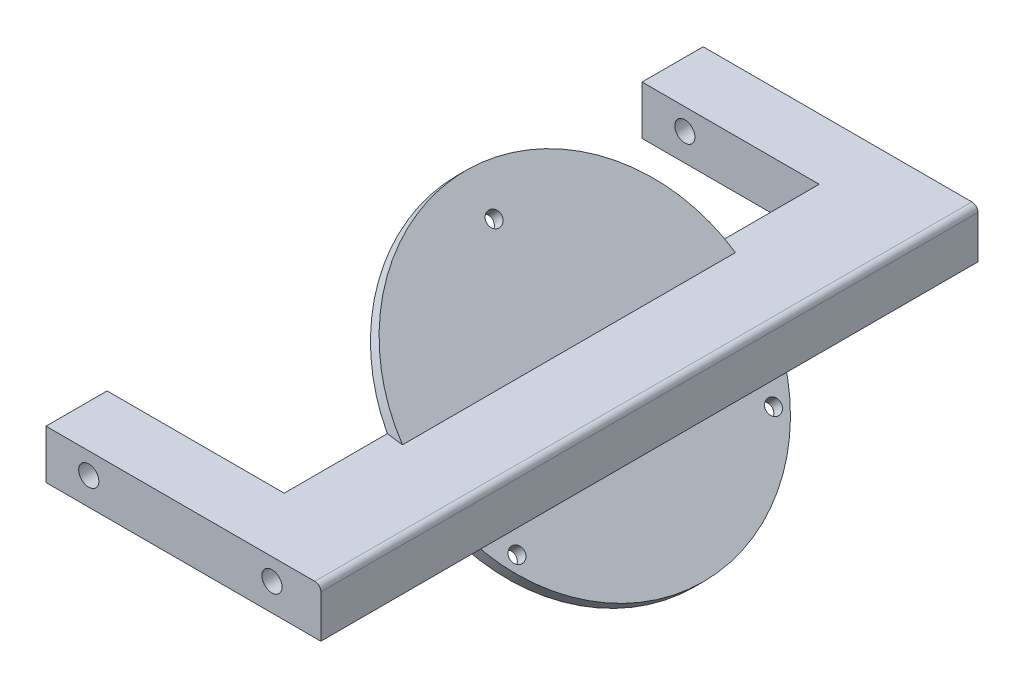
SolidWorks part; units mm, degrees
material "Nylon 101"
ref_plane "Front Plane" through (0, 0, 0) normal (0, 0, 1) x (1, 0, 0)
ref_plane "Top Plane" through (0, 0, 0) normal (0, 1, 0) x (1, 0, 0)
ref_plane "Right Plane" through (0, 0, 0) normal (1, 0, 0) x (0, 0, -1)
sketch "Sketch1" plane through (0, 0, 0) normal (0, 0, 1) x (1, 0, 0)
  line L4 (8, 4) -> (-8, 4)
  line L6 (0, -4) -> (-8, 4)
  line L7 (0, 4) -> (0, -4) construction
  line L8 (8, 4) -> (8, -4)
  line L9 (8, -4) -> (0, -4)
  dimension "D1" = 8
  dimension "D2" = 45
extrude "Base" add sketch "Sketch1" along normal mid plane 107.6
sketch "Sketch4" plane through (-2, -2, 0) normal (-0.7071, -0.7071, 0) x (0, 0, 1)
  line L0 (-53.8, 2.8284) -> (53.8, 2.8284) construction
  line L1 (-53.8, 8.4853) -> (-53.8, -2.8284) construction
  line L2 (53.8, 8.4853) -> (53.8, -2.8284) construction
  line L3 (0, 8.4853) -> (0, -2.8284) construction
  line L4 (53.8, 8.4853) -> (-53.8, 8.4853) construction
  line L6 (53.8, -2.8284) -> (-53.8, -2.8284) construction
  line L7 (-17.5, 20.3284) -> (17.5, 20.3284)
  line L8 (-17.5, 20.3284) -> (-17.5, -14.6716)
  line L9 (-17.5, -14.6716) -> (17.5, -14.6716)
  line L10 (17.5, 20.3284) -> (17.5, -14.6716)
  line L11 (-17.5, 20.3284) -> (17.5, -14.6716) construction
  line L12 (-17.5, -14.6716) -> (17.5, 20.3284) construction
  circle A0 centre (0, 2.8284) radius 27.5
  point P16 (0, 2.8284)
  point P17 (0, 2.8284)
  line M5 (53.8, 8.4853) -> (-53.8, 8.4853)
  dimension "D1" = 55
  dimension "D2" = 35
extrude "Boss-Extrude2" add sketch "Sketch4" against normal blind 2 contours A0 L8 L7 L10 M5 | L10 L7 L8 M5 | A0 L10 L9 L8 | A0 L8 M5 | L10 L8 L9 | L10 L8 M5 | A0 L10 M5 region at (-16.475, 12.475, 0) region at (-12.1872, 8.1872, 0) region at (0.1872, -4.1872, 0) region at (0.1872, -4.1872, -18.1422)
hole_wizard "M2 Clearance Hole1" positions "Sketch5" profile "Sketch6" hole size "M2" standard "ANSI Metric" end condition through all
sketch "Sketch5" plane through (-0.5858, -0.5858, 0) normal (0.7071, 0.7071, 0) x (0.7071, -0.7071, 0)
  line L4 (-8.4853, 0) -> (2.8284, 0) construction
  line L5 (-20.3284, 17.5) -> (-20.3284, -17.5) construction
  line L6 (-20.3284, -17.5) -> (14.6716, -17.5) construction
  line L7 (14.6716, 17.5) -> (14.6716, -17.5) construction
  line L8 (-20.3284, 17.5) -> (14.6716, 17.5) construction
  point P0 (-23.8284, 0)
  point P2 (11.1716, 21)
  point P4 (11.1716, -21)
  dimension "D1" = 3.5
  dimension "D2" = 3.5
  dimension "D3" = 3.5
  dimension "D4" = 3.5
sketch "Sketch6" plane through (-17.435, 16.2635, 0) normal (0, 0, 1) x (-0.7071, 0.7071, 0)
  line L0 (0, 0) -> (0, 29.5)
  line L1 (0, 29.5) -> (1.2, 29.5)
  line L2 (1.2, 29.5) -> (1.2, 0)
  line L5 (1.2, 0) -> (0, 0)
  line L11 (0, -6.35) -> (0, 107.95) construction
  dimension "Thru Hole Dia." = 2.4
  dimension "Thru Hole Depth" = 29.5
ref_plane "Plane1" through (-2, 2, 0) normal (0.7071, -0.7071, 0) x (0, 0, 1)
sketch "Sketch8" plane through (-2, 2, 0) normal (0.7071, -0.7071, 0) x (0, 0, 1)
  line L0 (0, 3.8284) -> (0, 2.8284)
  line L1 (27.5, 2.8284) -> (-27.5, 2.8284) construction
  line L2 (0, 2.8284) -> (-12, 2.8284)
  line L4 (0, 2.8284) -> (0, 10.3284) construction
  line L5 (-6.5, 10.3284) -> (-12, 2.8284)
  arc A1 (-6.5, 10.3284) -> (0, 3.8284) centre (0, 10.3284) ccw
  dimension "D2" = 6.5
  dimension "D1" = 1
  dimension "D3" = 12
revolve "Revolve1" add sketch "Sketch8" angle 360 about L4
fillet "Fillet1" radius 0.5 1 edges at (-13.8995, -0.7071, 0)
hole_wizard "Side Holes" positions "Sketch2" profile "Sketch3" hole size "Ø3.3" standard "ANSI Metric" end condition through all
sketch "Sketch2" plane through (0, 0, 53.8) normal (0, 0, 1) x (1, 0, 0)
  line L0 (0, 0.5) -> (0, 4) construction
  line L1 (8, 4) -> (-8, 4) construction
  line L3 (-4.5, 0.5) -> (8, 0.5) construction
  line L4 (-8, 4) -> (0, -4) construction
  line L6 (8, -4) -> (8, 4) construction
  point P0 (0, 0.5)
  dimension "D1" = 3.5
sketch "Sketch3" plane through (0, 0.5, 53.8) normal (1, 0, 0) x (0, -1, 0)
  line L0 (0, 0) -> (0, 107.6)
  line L1 (0, 107.6) -> (1.65, 107.6)
  line L2 (1.65, 107.6) -> (1.65, 0)
  line L5 (1.65, 0) -> (0, 0)
  line L11 (0, -6.35) -> (0, 107.95) construction
  dimension "Thru Hole Dia." = 3.3
  dimension "Thru Hole Depth" = 107.6
sketch "Sketch9" plane through (0, 0, 53.8) normal (0, 0, 1) x (1, 0, 0)
  line L0 (-8, 4) -> (0, -4)
  line L1 (0, -4) -> (-37, -4)
  line L2 (-37, -4) -> (-37, 4)
  line L3 (-37, 4) -> (-8, 4)
  line L4 (8, -4) -> (8, 4) construction
  dimension "D1" = 45
extrude "Side Arm" add sketch "Sketch9" against normal blind 10
mirror "Mirror1" about plane through (0, 0, 0) normal (0, 0, 1) of "Side Arm"
hole_wizard "Ø3.3 (3.3) Diameter Hole1" positions "Sketch10" profile "Sketch11" hole size "Ø3.3" standard "ANSI Metric" end condition through all
sketch "Sketch10" plane through (0, 0, 53.8) normal (0, 0, 1) x (1, 0, 0)
  line L0 (-37, 4) -> (-37, -4) construction
  point P0 (-30, 0.5)
  dimension "D1" = 7
sketch "Sketch11" plane through (-30, 0.5, 53.8) normal (1, 0, 0) x (0, -1, 0)
  line L0 (0, 0) -> (0, 107.6)
  line L1 (0, 107.6) -> (1.65, 107.6)
  line L2 (1.65, 107.6) -> (1.65, 0)
  line L5 (1.65, 0) -> (0, 0)
  line L11 (0, -6.35) -> (0, 107.95) construction
  dimension "Thru Hole Dia." = 3.3
  dimension "Thru Hole Depth" = 107.6
fillet "Fillet2" radius 1 1 edges at (8, 4, 0)
